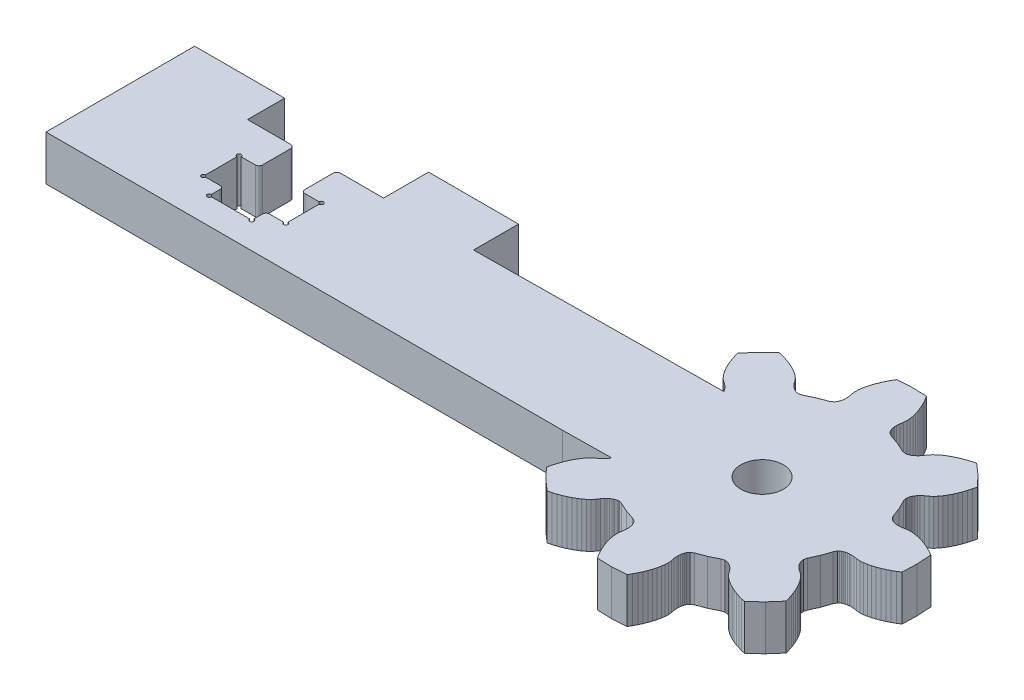
SolidWorks part; units mm, degrees
ref_plane "Front Plane" through (0, 0, 0) normal (0, 0, 1) x (1, 0, 0)
ref_plane "Top Plane" through (0, 0, 0) normal (0, 1, 0) x (1, 0, 0)
ref_plane "Right Plane" through (0, 0, 0) normal (1, 0, 0) x (0, 0, -1)
sketch "Sketch1" plane through (0, 0, 0) normal (0, 1, 0) x (1, 0, 0)
  line L0 (63.4907, 166.1354) -> (63.4907, 169.3104)
  line L1 (63.4907, 169.3104) -> (57.1407, 169.3104)
  line L2 (57.1407, 169.3104) -> (57.1407, 166.1354)
  line L3 (57.1407, 166.1354) -> (54.0907, 166.1354)
  line L4 (47.5407, 166.1354) -> (47.5407, 168.7529)
  line L5 (47.5407, 168.7529) -> (41.1907, 168.7529)
  line L6 (41.1907, 168.7529) -> (41.1907, 158.2613)
  line L7 (41.1907, 158.2613) -> (77.6477, 158.2613)
  line L8 (52.3407, 166.1354) -> (52.3407, 155.7177) construction
  line L9 (50.8407, 165.8854) -> (50.8407, 163.8854)
  line L10 (50.5907, 163.6354) -> (49.5907, 163.6354)
  line L11 (49.4407, 163.4854) -> (49.4407, 161.2854)
  line L12 (49.5907, 161.1354) -> (50.5907, 161.1354)
  line L13 (50.8407, 160.8854) -> (50.8407, 160.2854)
  line L14 (50.9907, 160.1354) -> (53.6907, 160.1354)
  line L15 (53.8407, 160.8854) -> (53.8407, 160.2854)
  line L16 (55.0907, 161.1354) -> (54.0907, 161.1354)
  line L17 (55.2407, 163.4854) -> (55.2407, 161.2854)
  line L18 (54.0907, 163.6354) -> (55.0907, 163.6354)
  line L19 (53.8407, 165.8854) -> (53.8407, 163.8854)
  line L20 (50.5907, 166.1354) -> (47.5407, 166.1354)
  line L1268 (81.0578, 158.2714) -> (81.0243, 158.3054)
  line L1269 (81.0243, 158.3054) -> (77.6477, 158.2613)
  line L1276 (63.4907, 166.1354) -> (80.9763, 166.3177)
  line L1277 (80.9763, 166.3177) -> (80.9618, 166.3272)
  line L1278 (80.9618, 166.3272) -> (80.9303, 166.3857)
  line L1279 (80.9303, 166.3857) -> (80.8605, 166.4907)
  line L1280 (80.8605, 166.4907) -> (80.7838, 166.5839)
  line L1281 (80.7838, 166.5839) -> (80.7017, 166.668)
  line L1282 (80.7017, 166.668) -> (80.5246, 166.8149)
  line L1283 (80.5246, 166.8149) -> (80.3334, 166.9392)
  line L1284 (80.3334, 166.9392) -> (80.1557, 167.0849)
  line L1285 (80.1557, 167.0849) -> (79.9967, 167.2599)
  line L1286 (79.9967, 167.2599) -> (79.8501, 167.4532)
  line L1287 (79.8501, 167.4532) -> (79.7145, 167.6617)
  line L1288 (79.7145, 167.6617) -> (79.5894, 167.8837)
  line L1289 (79.5894, 167.8837) -> (79.4745, 168.1179)
  line L1290 (79.4745, 168.1179) -> (79.3699, 168.3635)
  line L1291 (79.3699, 168.3635) -> (79.2754, 168.6197)
  line L1292 (79.2754, 168.6197) -> (79.1915, 168.886)
  line L1293 (79.1915, 168.886) -> (79.1181, 169.1617)
  line L1294 (79.1181, 169.1617) -> (79.8009, 169.9374)
  line L1295 (79.8009, 169.9374) -> (80.5548, 170.6443)
  line L1296 (80.5548, 170.6443) -> (80.8327, 170.5796)
  line L1297 (80.8327, 170.5796) -> (81.1014, 170.504)
  line L1298 (81.1014, 170.504) -> (81.3605, 170.4177)
  line L1299 (81.3605, 170.4177) -> (81.6093, 170.3208)
  line L1300 (81.6093, 170.3208) -> (81.847, 170.2133)
  line L1301 (81.847, 170.2133) -> (82.0728, 170.0952)
  line L1302 (82.0728, 170.0952) -> (82.2854, 169.9663)
  line L1303 (82.2854, 169.9663) -> (82.4832, 169.8259)
  line L1304 (82.4832, 169.8259) -> (82.6631, 169.6724)
  line L1305 (82.6631, 169.6724) -> (82.8144, 169.4994)
  line L1306 (82.8144, 169.4994) -> (82.9446, 169.3122)
  line L1307 (82.9446, 169.3122) -> (83.097, 169.1398)
  line L1308 (83.097, 169.1398) -> (83.1836, 169.0603)
  line L1309 (83.1836, 169.0603) -> (83.2792, 168.9866)
  line L1310 (83.2792, 168.9866) -> (83.3864, 168.9201)
  line L1311 (83.3864, 168.9201) -> (83.4458, 168.8905)
  line L1312 (83.4458, 168.8905) -> (83.5105, 168.8639)
  line L1313 (83.5105, 168.8639) -> (83.5824, 168.8415)
  line L1314 (83.5824, 168.8415) -> (83.6651, 168.8253)
  line L1315 (83.6651, 168.8253) -> (83.768, 168.8205)
  line L1316 (83.768, 168.8205) -> (83.9876, 168.8804)
  line L1317 (83.9876, 168.8804) -> (84.6212, 169.1914)
  line L1318 (84.6212, 169.1914) -> (85.2815, 169.4403)
  line L1319 (85.2815, 169.4403) -> (85.4756, 169.5595)
  line L1320 (85.4756, 169.5595) -> (85.5425, 169.6378)
  line L1321 (85.5425, 169.6378) -> (85.5873, 169.7091)
  line L1322 (85.5873, 169.7091) -> (85.6202, 169.7768)
  line L1323 (85.6202, 169.7768) -> (85.6451, 169.8422)
  line L1324 (85.6451, 169.8422) -> (85.6641, 169.9058)
  line L1325 (85.6641, 169.9058) -> (85.6891, 170.0295)
  line L1326 (85.6891, 170.0295) -> (85.7007, 170.1496)
  line L1327 (85.7007, 170.1496) -> (85.7022, 170.2671)
  line L1328 (85.7022, 170.2671) -> (85.6808, 170.4962)
  line L1329 (85.6808, 170.4962) -> (85.6334, 170.7193)
  line L1330 (85.6334, 170.7193) -> (85.6109, 170.948)
  line L1331 (85.6109, 170.948) -> (85.6222, 171.1842)
  line L1332 (85.6222, 171.1842) -> (85.6552, 171.4245)
  line L1333 (85.6552, 171.4245) -> (85.7068, 171.6678)
  line L1334 (85.7068, 171.6678) -> (85.7752, 171.9132)
  line L1335 (85.7752, 171.9132) -> (85.8596, 172.1601)
  line L1336 (85.8596, 172.1601) -> (85.9593, 172.4078)
  line L1337 (85.9593, 172.4078) -> (86.0737, 172.6557)
  line L1338 (86.0737, 172.6557) -> (86.2026, 172.9034)
  line L1339 (86.2026, 172.9034) -> (86.3457, 173.1502)
  line L1340 (86.3457, 173.1502) -> (87.377, 173.2159)
  line L1341 (87.377, 173.2159) -> (88.4099, 173.1826)
  line L1342 (88.4099, 173.1826) -> (88.5607, 172.9404)
  line L1343 (88.5607, 172.9404) -> (88.6973, 172.6969)
  line L1344 (88.6973, 172.6969) -> (88.8195, 172.4527)
  line L1345 (88.8195, 172.4527) -> (88.9268, 172.2082)
  line L1346 (88.9268, 172.2082) -> (89.0189, 171.9642)
  line L1347 (89.0189, 171.9642) -> (89.0951, 171.721)
  line L1348 (89.0951, 171.721) -> (89.1543, 171.4795)
  line L1349 (89.1543, 171.4795) -> (89.1948, 171.2403)
  line L1350 (89.1948, 171.2403) -> (89.2136, 171.0046)
  line L1351 (89.2136, 171.0046) -> (89.1981, 170.7753)
  line L1352 (89.1981, 170.7753) -> (89.1579, 170.5508)
  line L1353 (89.1579, 170.5508) -> (89.1437, 170.3212)
  line L1354 (89.1437, 170.3212) -> (89.1488, 170.2038)
  line L1355 (89.1488, 170.2038) -> (89.1642, 170.0841)
  line L1356 (89.1642, 170.0841) -> (89.193, 169.9613)
  line L1357 (89.193, 169.9613) -> (89.214, 169.8982)
  line L1358 (89.214, 169.8982) -> (89.241, 169.8337)
  line L1359 (89.241, 169.8337) -> (89.276, 169.7671)
  line L1360 (89.276, 169.7671) -> (89.3231, 169.6971)
  line L1361 (89.3231, 169.6971) -> (89.3924, 169.621)
  line L1362 (89.3924, 169.621) -> (89.59, 169.508)
  line L1363 (89.59, 169.508) -> (90.2579, 169.28)
  line L1364 (90.2579, 169.28) -> (90.9009, 168.989)
  line L1365 (90.9009, 168.989) -> (91.1223, 168.9361)
  line L1366 (91.1223, 168.9361) -> (91.225, 168.9441)
  line L1367 (91.225, 168.9441) -> (91.3072, 168.9629)
  line L1368 (91.3072, 168.9629) -> (91.3783, 168.9875)
  line L1369 (91.3783, 168.9875) -> (91.4422, 169.0161)
  line L1370 (91.4422, 169.0161) -> (91.5006, 169.0476)
  line L1371 (91.5006, 169.0476) -> (91.6057, 169.1174)
  line L1372 (91.6057, 169.1174) -> (91.6989, 169.1941)
  line L1373 (91.6989, 169.1941) -> (91.7829, 169.2762)
  line L1374 (91.7829, 169.2762) -> (91.9298, 169.4533)
  line L1375 (91.9298, 169.4533) -> (92.0541, 169.6445)
  line L1376 (92.0541, 169.6445) -> (92.1999, 169.8223)
  line L1377 (92.1999, 169.8223) -> (92.3749, 169.9812)
  line L1378 (92.3749, 169.9812) -> (92.5682, 170.1278)
  line L1379 (92.5682, 170.1278) -> (92.7767, 170.2634)
  line L1380 (92.7767, 170.2634) -> (92.9986, 170.3885)
  line L1381 (92.9986, 170.3885) -> (93.2328, 170.5034)
  line L1382 (93.2328, 170.5034) -> (93.4784, 170.6081)
  line L1383 (93.4784, 170.6081) -> (93.7347, 170.7025)
  line L1384 (93.7347, 170.7025) -> (94.001, 170.7864)
  line L1385 (94.001, 170.7864) -> (94.2766, 170.8598)
  line L1386 (94.2766, 170.8598) -> (95.0524, 170.177)
  line L1387 (95.0524, 170.177) -> (95.7592, 169.4231)
  line L1388 (95.7592, 169.4231) -> (95.6945, 169.1453)
  line L1389 (95.6945, 169.1453) -> (95.6189, 168.8765)
  line L1390 (95.6189, 168.8765) -> (95.5327, 168.6174)
  line L1391 (95.5327, 168.6174) -> (95.4357, 168.3686)
  line L1392 (95.4357, 168.3686) -> (95.3283, 168.1309)
  line L1393 (95.3283, 168.1309) -> (95.2102, 167.9051)
  line L1394 (95.2102, 167.9051) -> (95.0812, 167.6925)
  line L1395 (95.0812, 167.6925) -> (94.9408, 167.4947)
  line L1396 (94.9408, 167.4947) -> (94.7874, 167.3148)
  line L1397 (94.7874, 167.3148) -> (94.6144, 167.1635)
  line L1398 (94.6144, 167.1635) -> (94.4271, 167.0333)
  line L1399 (94.4271, 167.0333) -> (94.2547, 166.8809)
  line L1400 (94.2547, 166.8809) -> (94.1753, 166.7943)
  line L1401 (94.1753, 166.7943) -> (94.1016, 166.6988)
  line L1402 (94.1016, 166.6988) -> (94.0351, 166.5915)
  line L1403 (94.0351, 166.5915) -> (94.0054, 166.5321)
  line L1404 (94.0054, 166.5321) -> (93.9788, 166.4674)
  line L1405 (93.9788, 166.4674) -> (93.9565, 166.3955)
  line L1406 (93.9565, 166.3955) -> (93.9403, 166.3128)
  line L1407 (93.9403, 166.3128) -> (93.9355, 166.21)
  line L1408 (93.9355, 166.21) -> (93.9954, 165.9903)
  line L1409 (93.9954, 165.9903) -> (94.3064, 165.3568)
  line L1410 (94.3064, 165.3568) -> (94.5553, 164.6964)
  line L1411 (94.5553, 164.6964) -> (94.6744, 164.5024)
  line L1412 (94.6744, 164.5024) -> (94.7527, 164.4354)
  line L1413 (94.7527, 164.4354) -> (94.824, 164.3906)
  line L1414 (94.824, 164.3906) -> (94.8918, 164.3578)
  line L1415 (94.8918, 164.3578) -> (94.9571, 164.3328)
  line L1416 (94.9571, 164.3328) -> (95.0208, 164.3138)
  line L1417 (95.0208, 164.3138) -> (95.1444, 164.2888)
  line L1418 (95.1444, 164.2888) -> (95.2645, 164.2772)
  line L1419 (95.2645, 164.2772) -> (95.382, 164.2758)
  line L1420 (95.382, 164.2758) -> (95.6112, 164.2972)
  line L1421 (95.6112, 164.2972) -> (95.8342, 164.3445)
  line L1422 (95.8342, 164.3445) -> (96.063, 164.3671)
  line L1423 (96.063, 164.3671) -> (96.2992, 164.3557)
  line L1424 (96.2992, 164.3557) -> (96.5395, 164.3227)
  line L1425 (96.5395, 164.3227) -> (96.7828, 164.2712)
  line L1426 (96.7828, 164.2712) -> (97.0282, 164.2027)
  line L1427 (97.0282, 164.2027) -> (97.275, 164.1183)
  line L1428 (97.275, 164.1183) -> (97.5227, 164.0186)
  line L1429 (97.5227, 164.0186) -> (97.7707, 163.9042)
  line L1430 (97.7707, 163.9042) -> (98.0183, 163.7753)
  line L1431 (98.0183, 163.7753) -> (98.2652, 163.6323)
  line L1432 (98.2652, 163.6323) -> (98.3308, 162.6009)
  line L1433 (98.3308, 162.6009) -> (98.2976, 161.568)
  line L1434 (98.2976, 161.568) -> (98.0554, 161.4173)
  line L1435 (98.0554, 161.4173) -> (97.8119, 161.2806)
  line L1436 (97.8119, 161.2806) -> (97.5677, 161.1585)
  line L1437 (97.5677, 161.1585) -> (97.3232, 161.0511)
  line L1438 (97.3232, 161.0511) -> (97.0791, 160.959)
  line L1439 (97.0791, 160.959) -> (96.836, 160.8829)
  line L1440 (96.836, 160.8829) -> (96.5944, 160.8237)
  line L1441 (96.5944, 160.8237) -> (96.3553, 160.7831)
  line L1442 (96.3553, 160.7831) -> (96.1196, 160.7644)
  line L1443 (96.1196, 160.7644) -> (95.8903, 160.7798)
  line L1444 (95.8903, 160.7798) -> (95.6658, 160.8201)
  line L1445 (95.6658, 160.8201) -> (95.4361, 160.8342)
  line L1446 (95.4361, 160.8342) -> (95.3187, 160.8291)
  line L1447 (95.3187, 160.8291) -> (95.199, 160.8137)
  line L1448 (95.199, 160.8137) -> (95.0762, 160.7849)
  line L1449 (95.0762, 160.7849) -> (95.0132, 160.7639)
  line L1450 (95.0132, 160.7639) -> (94.9487, 160.7369)
  line L1451 (94.9487, 160.7369) -> (94.882, 160.7019)
  line L1452 (94.882, 160.7019) -> (94.8121, 160.6549)
  line L1453 (94.8121, 160.6549) -> (94.736, 160.5855)
  line L1454 (94.736, 160.5855) -> (94.623, 160.3879)
  line L1455 (94.623, 160.3879) -> (94.3949, 159.72)
  line L1456 (94.3949, 159.72) -> (94.1039, 159.077)
  line L1457 (94.1039, 159.077) -> (94.051, 158.8556)
  line L1458 (94.051, 158.8556) -> (94.0591, 158.7529)
  line L1459 (94.0591, 158.7529) -> (94.0778, 158.6708)
  line L1460 (94.0778, 158.6708) -> (94.1025, 158.5996)
  line L1461 (94.1025, 158.5996) -> (94.131, 158.5358)
  line L1462 (94.131, 158.5358) -> (94.1626, 158.4773)
  line L1463 (94.1626, 158.4773) -> (94.2324, 158.3722)
  line L1464 (94.2324, 158.3722) -> (94.3091, 158.2791)
  line L1465 (94.3091, 158.2791) -> (94.3912, 158.195)
  line L1466 (94.3912, 158.195) -> (94.5683, 158.0481)
  line L1467 (94.5683, 158.0481) -> (94.7595, 157.9238)
  line L1468 (94.7595, 157.9238) -> (94.9372, 157.778)
  line L1469 (94.9372, 157.778) -> (95.0962, 157.603)
  line L1470 (95.0962, 157.603) -> (95.2427, 157.4097)
  line L1471 (95.2427, 157.4097) -> (95.3783, 157.2013)
  line L1472 (95.3783, 157.2013) -> (95.5035, 156.9793)
  line L1473 (95.5035, 156.9793) -> (95.6184, 156.7451)
  line L1474 (95.6184, 156.7451) -> (95.723, 156.4995)
  line L1475 (95.723, 156.4995) -> (95.8174, 156.2432)
  line L1476 (95.8174, 156.2432) -> (95.9014, 155.9769)
  line L1477 (95.9014, 155.9769) -> (95.9748, 155.7013)
  line L1478 (95.9748, 155.7013) -> (95.292, 154.9255)
  line L1479 (95.292, 154.9255) -> (94.5381, 154.2187)
  line L1480 (94.5381, 154.2187) -> (94.2602, 154.2834)
  line L1481 (94.2602, 154.2834) -> (93.9914, 154.359)
  line L1482 (93.9914, 154.359) -> (93.7324, 154.4453)
  line L1483 (93.7324, 154.4453) -> (93.4836, 154.5422)
  line L1484 (93.4836, 154.5422) -> (93.2458, 154.6496)
  line L1485 (93.2458, 154.6496) -> (93.0201, 154.7677)
  line L1486 (93.0201, 154.7677) -> (92.8074, 154.8967)
  line L1487 (92.8074, 154.8967) -> (92.6097, 155.0371)
  line L1488 (92.6097, 155.0371) -> (92.4297, 155.1905)
  line L1489 (92.4297, 155.1905) -> (92.2785, 155.3636)
  line L1490 (92.2785, 155.3636) -> (92.1482, 155.5508)
  line L1491 (92.1482, 155.5508) -> (91.9959, 155.7232)
  line L1492 (91.9959, 155.7232) -> (91.9092, 155.8026)
  line L1493 (91.9092, 155.8026) -> (91.8137, 155.8763)
  line L1494 (91.8137, 155.8763) -> (91.7065, 155.9428)
  line L1495 (91.7065, 155.9428) -> (91.6471, 155.9725)
  line L1496 (91.6471, 155.9725) -> (91.5824, 155.9991)
  line L1497 (91.5824, 155.9991) -> (91.5105, 156.0215)
  line L1498 (91.5105, 156.0215) -> (91.4278, 156.0376)
  line L1499 (91.4278, 156.0376) -> (91.3249, 156.0424)
  line L1500 (91.3249, 156.0424) -> (91.1052, 155.9826)
  line L1501 (91.1052, 155.9826) -> (90.4717, 155.6716)
  line L1502 (90.4717, 155.6716) -> (89.8113, 155.4226)
  line L1503 (89.8113, 155.4226) -> (89.6173, 155.3035)
  line L1504 (89.6173, 155.3035) -> (89.5504, 155.2252)
  line L1505 (89.5504, 155.2252) -> (89.5056, 155.1539)
  line L1506 (89.5056, 155.1539) -> (89.4727, 155.0862)
  line L1507 (89.4727, 155.0862) -> (89.4478, 155.0208)
  line L1508 (89.4478, 155.0208) -> (89.4287, 154.9571)
  line L1509 (89.4287, 154.9571) -> (89.4038, 154.8335)
  line L1510 (89.4038, 154.8335) -> (89.3921, 154.7134)
  line L1511 (89.3921, 154.7134) -> (89.3907, 154.5959)
  line L1512 (89.3907, 154.5959) -> (89.4121, 154.3667)
  line L1513 (89.4121, 154.3667) -> (89.4594, 154.1437)
  line L1514 (89.4594, 154.1437) -> (89.482, 153.9149)
  line L1515 (89.482, 153.9149) -> (89.4707, 153.6788)
  line L1516 (89.4707, 153.6788) -> (89.4377, 153.4385)
  line L1517 (89.4377, 153.4385) -> (89.3861, 153.1952)
  line L1518 (89.3861, 153.1952) -> (89.3176, 152.9497)
  line L1519 (89.3176, 152.9497) -> (89.2332, 152.7029)
  line L1520 (89.2332, 152.7029) -> (89.1336, 152.4552)
  line L1521 (89.1336, 152.4552) -> (89.0191, 152.2072)
  line L1522 (89.0191, 152.2072) -> (88.8903, 151.9596)
  line L1523 (88.8903, 151.9596) -> (88.7472, 151.7128)
  line L1524 (88.7472, 151.7128) -> (87.7159, 151.6471)
  line L1525 (87.7159, 151.6471) -> (86.6829, 151.6804)
  line L1526 (86.6829, 151.6804) -> (86.5322, 151.9226)
  line L1527 (86.5322, 151.9226) -> (86.3956, 152.166)
  line L1528 (86.3956, 152.166) -> (86.2734, 152.4103)
  line L1529 (86.2734, 152.4103) -> (86.166, 152.6547)
  line L1530 (86.166, 152.6547) -> (86.0739, 152.8988)
  line L1531 (86.0739, 152.8988) -> (85.9978, 153.1419)
  line L1532 (85.9978, 153.1419) -> (85.9386, 153.3835)
  line L1533 (85.9386, 153.3835) -> (85.8981, 153.6226)
  line L1534 (85.8981, 153.6226) -> (85.8793, 153.8584)
  line L1535 (85.8793, 153.8584) -> (85.8947, 154.0877)
  line L1536 (85.8947, 154.0877) -> (85.935, 154.3121)
  line L1537 (85.935, 154.3121) -> (85.9492, 154.5418)
  line L1538 (85.9492, 154.5418) -> (85.9441, 154.6592)
  line L1539 (85.9441, 154.6592) -> (85.9287, 154.7789)
  line L1540 (85.9287, 154.7789) -> (85.8999, 154.9017)
  line L1541 (85.8999, 154.9017) -> (85.8788, 154.9647)
  line L1542 (85.8788, 154.9647) -> (85.8518, 155.0293)
  line L1543 (85.8518, 155.0293) -> (85.8168, 155.0959)
  line L1544 (85.8168, 155.0959) -> (85.7698, 155.1658)
  line L1545 (85.7698, 155.1658) -> (85.7005, 155.242)
  line L1546 (85.7005, 155.242) -> (85.5028, 155.3549)
  line L1547 (85.5028, 155.3549) -> (84.8349, 155.583)
  line L1548 (84.8349, 155.583) -> (84.1919, 155.874)
  line L1549 (84.1919, 155.874) -> (83.9705, 155.9269)
  line L1550 (83.9705, 155.9269) -> (83.8679, 155.9189)
  line L1551 (83.8679, 155.9189) -> (83.7857, 155.9001)
  line L1552 (83.7857, 155.9001) -> (83.7146, 155.8755)
  line L1553 (83.7146, 155.8755) -> (83.6507, 155.8469)
  line L1554 (83.6507, 155.8469) -> (83.5922, 155.8153)
  line L1555 (83.5922, 155.8153) -> (83.4872, 155.7456)
  line L1556 (83.4872, 155.7456) -> (83.394, 155.6689)
  line L1557 (83.394, 155.6689) -> (83.3099, 155.5868)
  line L1558 (83.3099, 155.5868) -> (83.163, 155.4096)
  line L1559 (83.163, 155.4096) -> (83.0388, 155.2184)
  line L1560 (83.0388, 155.2184) -> (82.893, 155.0407)
  line L1561 (82.893, 155.0407) -> (82.718, 154.8817)
  line L1562 (82.718, 154.8817) -> (82.5247, 154.7352)
  line L1563 (82.5247, 154.7352) -> (82.3162, 154.5996)
  line L1564 (82.3162, 154.5996) -> (82.0943, 154.4745)
  line L1565 (82.0943, 154.4745) -> (81.86, 154.3596)
  line L1566 (81.86, 154.3596) -> (81.6144, 154.2549)
  line L1567 (81.6144, 154.2549) -> (81.3582, 154.1605)
  line L1568 (81.3582, 154.1605) -> (81.0919, 154.0765)
  line L1569 (81.0919, 154.0765) -> (80.8162, 154.0031)
  line L1570 (80.8162, 154.0031) -> (80.0405, 154.686)
  line L1571 (80.0405, 154.686) -> (79.3336, 155.4399)
  line L1572 (79.3336, 155.4399) -> (79.3983, 155.7177)
  line L1573 (79.3983, 155.7177) -> (79.4739, 155.9865)
  line L1574 (79.4739, 155.9865) -> (79.5602, 156.2456)
  line L1575 (79.5602, 156.2456) -> (79.6571, 156.4943)
  line L1576 (79.6571, 156.4943) -> (79.7646, 156.7321)
  line L1577 (79.7646, 156.7321) -> (79.8827, 156.9578)
  line L1578 (79.8827, 156.9578) -> (80.0116, 157.1705)
  line L1579 (80.0116, 157.1705) -> (80.1521, 157.3682)
  line L1580 (80.1521, 157.3682) -> (80.3055, 157.5482)
  line L1581 (80.3055, 157.5482) -> (80.4785, 157.6995)
  line L1582 (80.4785, 157.6995) -> (80.6657, 157.8297)
  line L1583 (80.6657, 157.8297) -> (80.8382, 157.9821)
  line L1584 (80.8382, 157.9821) -> (80.9176, 158.0687)
  line L1585 (80.9176, 158.0687) -> (80.9913, 158.1642)
  line L1586 (80.9913, 158.1642) -> (81.0578, 158.2714)
  circle A0 centre (87.5463, 162.4441) radius 1.5001
  arc A1 (49.5907, 163.6354) -> (49.4407, 163.4854) centre (49.4407, 163.6354) ccw
  arc A2 (49.4407, 161.2854) -> (49.5907, 161.1354) centre (49.4407, 161.1354) ccw
  arc A3 (50.8407, 160.2854) -> (50.9907, 160.1354) centre (50.8407, 160.1354) ccw
  arc A4 (50.5907, 161.1354) -> (50.8407, 160.8854) centre (50.5907, 160.8854) cw
  arc A5 (50.8407, 163.8854) -> (50.5907, 163.6354) centre (50.5907, 163.8854) cw
  arc A6 (53.8407, 163.8854) -> (54.0907, 163.6354) centre (54.0907, 163.8854) ccw
  arc A7 (54.0907, 161.1354) -> (53.8407, 160.8854) centre (54.0907, 160.8854) ccw
  arc A8 (53.8407, 160.2854) -> (53.6907, 160.1354) centre (53.8407, 160.1354) cw
  arc A9 (55.2407, 161.2854) -> (55.0907, 161.1354) centre (55.2407, 161.1354) cw
  arc A10 (55.0907, 163.6354) -> (55.2407, 163.4854) centre (55.2407, 163.6354) cw
  arc A11 (53.8407, 165.8854) -> (54.0907, 166.1354) centre (54.0907, 165.8854) cw
  arc A12 (50.8407, 165.8854) -> (50.5907, 166.1354) centre (50.5907, 165.8854) ccw
  point P26 (50.8407, 161.1354)
  point P29 (50.8407, 163.6354)
  point P45 (52.3407, 160.1354)
  point P46 (53.8407, 163.6354)
  point P47 (53.8407, 161.1354)
  point P50 (53.8407, 166.1354)
  point P53 (50.8407, 166.1354)
  dimension "D11" = 0.3
  dimension "D12" = 0.3
  dimension "D13" = 0.3
  dimension "D14" = 0.25
  dimension "D15" = 0.25
  dimension "D1" = 6.35
  dimension "D2" = 3.175
  dimension "D3" = 6.35
  dimension "D4" = 9.6
  dimension "D5" = 2.5
  dimension "D6" = 2.5
  dimension "D7" = 1
  dimension "D8" = 1.5
  dimension "D9" = 2.9
  dimension "D10" = 1.5
extrude "Boss-Extrude1" add sketch "Sketch1" along normal blind 3.175
